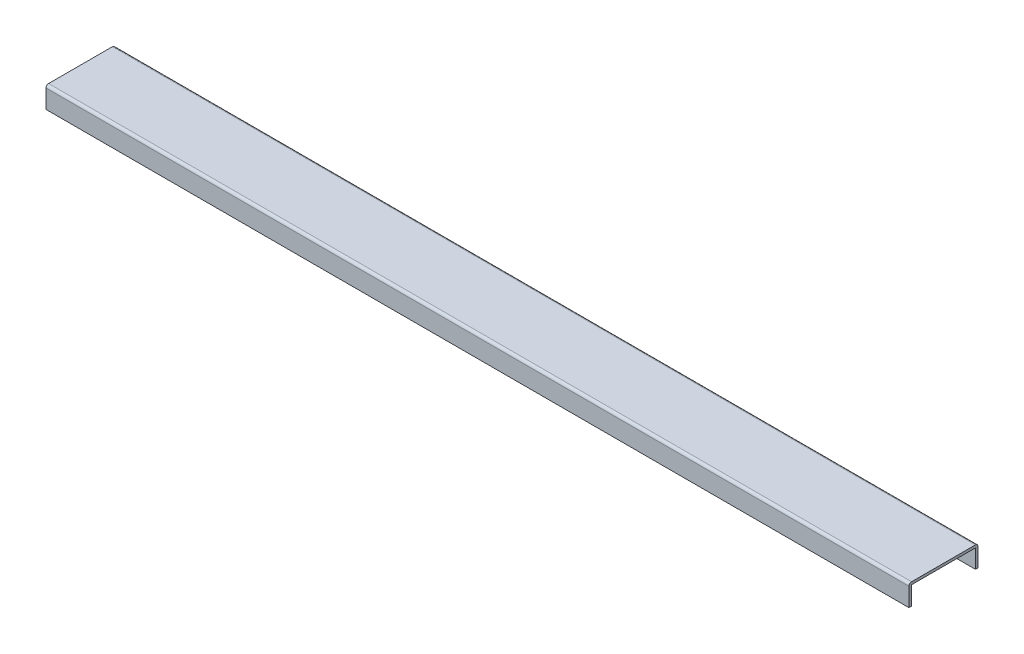
SolidWorks part; units mm, degrees
ref_plane "Спереди" through (0, 0, 0) normal (0, 0, 1) x (1, 0, 0)
ref_plane "Сверху" through (0, 0, 0) normal (0, 1, 0) x (1, 0, 0)
ref_plane "Справа" through (0, 0, 0) normal (1, 0, 0) x (0, 0, -1)
sketch "Эскиз1" plane through (0, 0, 0) normal (1, 0, 0) x (0, 0, -1)
  line L1 (3, 0) -> (77, 0)
  line L2 (0, 3) -> (0, 77)
  line L3 (3, 80) -> (77, 80)
  line L4 (80, 3) -> (80, 77)
  arc A0 (0, 3) -> (3, 0) centre (3, 3) ccw
  arc A1 (77, 0) -> (80, 3) centre (77, 3) ccw
  arc A2 (77, 80) -> (80, 77) centre (77, 77) cw
  arc A3 (0, 77) -> (3, 80) centre (3, 77) cw
  point P7 (0, 0)
  dimension "D1" = 3
extrude "Вытянуть-Тонкостенный1" add sketch "Эскиз1" along normal blind 1000 thin thin type one direction reverse wall 3
sketch "Эскиз2" plane through (0, 0, -80) normal (0, 0, -1) x (-1, 0, 0)
  line L0 (0, 3) -> (0, 77) construction
  line L1 (-1000, 0) -> (0, 0)
  line L2 (-1000, 0) -> (-1000, 55.462)
  line L3 (-1000, 55.462) -> (0, 55.462)
  line L4 (0, 0) -> (0, 55.462)
extrude "Вырез-Вытянуть1" cut sketch "Эскиз2" against normal through all
